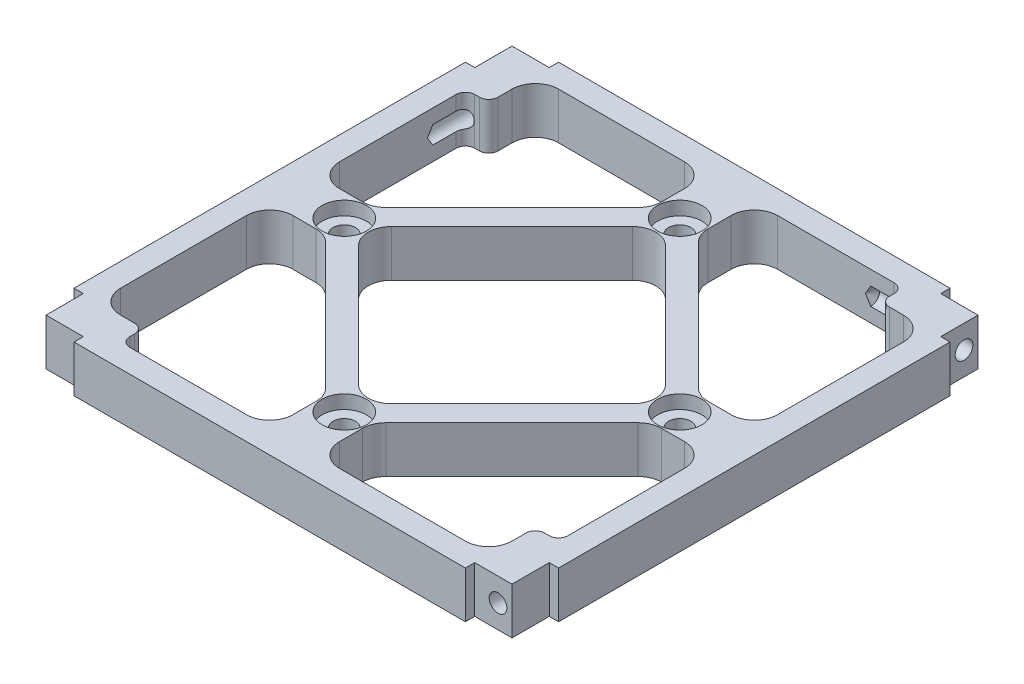
SolidWorks part; units mm, degrees
material "6061-T6 (SS)"
ref_plane "Front Plane" through (0, 0, 0) normal (0, 0, 1) x (1, 0, 0)
ref_plane "Top Plane" through (0, 0, 0) normal (0, 1, 0) x (1, 0, 0)
ref_plane "Right Plane" through (0, 0, 0) normal (1, 0, 0) x (0, 0, -1)
sketch "Sketch1" plane through (0, 0, 0) normal (0, 1, 0) x (1, 0, 0)
  line L0 (-42, 47) -> (-42, 37)
  line L1 (-52, 52) -> (52, 52)
  line L2 (-52, 52) -> (-52, -52)
  line L3 (-52, -52) -> (52, -52)
  line L4 (52, 52) -> (52, -52)
  line L5 (-47, 5) -> (-35, 5)
  line L6 (-35, 5) -> (-5, 35)
  line L7 (-5, 35) -> (-5, 47)
  line L8 (-5, 47) -> (-42, 47)
  line L9 (0, 0) -> (0, 76.3292) construction
  line L10 (0, 0) -> (-78.8537, 0) construction
  line L11 (0, 0) -> (-66.7994, 66.7994) construction
  line L12 (-32.9289, 0) -> (0, 32.9289)
  line L13 (0, 32.9289) -> (32.9289, 0)
  line L14 (32.9289, 0) -> (0, -32.9289)
  line L15 (0, -32.9289) -> (-32.9289, 0)
  line L16 (5, 47) -> (5, 35)
  line L17 (37, 47) -> (5, 47)
  line L18 (37, 42) -> (37, 47)
  line L19 (47, 42) -> (37, 42)
  line L20 (47, 5) -> (47, 42)
  line L21 (35, 5) -> (47, 5)
  line L22 (5, 35) -> (35, 5)
  line L23 (47, -5) -> (35, -5)
  line L24 (47, -37) -> (47, -5)
  line L25 (42, -37) -> (47, -37)
  line L26 (42, -47) -> (42, -37)
  line L27 (5, -47) -> (42, -47)
  line L28 (5, -35) -> (5, -47)
  line L29 (35, -5) -> (5, -35)
  line L30 (-5, -47) -> (-5, -35)
  line L31 (-42, 37) -> (-47, 37)
  line L32 (-47, 37) -> (-47, 5)
  line L33 (-37, -47) -> (-5, -47)
  line L34 (-37, -42) -> (-37, -47)
  line L35 (-47, -42) -> (-37, -42)
  line L36 (-47, -5) -> (-47, -42)
  line L37 (-35, -5) -> (-47, -5)
  line L38 (-5, -35) -> (-35, -5)
  point P36 (0.1996, 0.1996)
  point P45 (0, 0)
  dimension "D1" = 104
  dimension "D2" = 5
  dimension "D3" = 5
  dimension "D4" = 5
  dimension "D5" = 5
  dimension "D6" = 5
  dimension "D7" = 12
  dimension "D8" = 10
  dimension "D9" = 10
  dimension "D10" = 4
extrude "Boss-Extrude1" add sketch "Sketch1" along normal blind 10
fillet "Fillet1" radius 5 24 edges at (32.9289, 5, 0) (0, 5, 32.9289) (-32.9289, 5, 0) (0, 5, -32.9289) (-5, 5, -47) (-5, 5, -35) (-35, 5, -5) (-47, 5, 42) (-47, 5, 5) (-35, 5, 5) (-5, 5, 35) (-5, 5, 47) (42, 5, 47) (47, 5, 5) (35, 5, 5) (5, 5, 35) (5, 5, 47) (47, 5, -42) (47, 5, -5) (35, 5, -5) (5, 5, -35) (5, 5, -47) (-42, 5, -47) (-47, 5, -5)
sketch "Sketch2" plane through (0, 10, 0) normal (0, 1, 0) x (1, 0, 0)
  line L0 (-52, 52) -> (-42, 52)
  line L1 (52, 52) -> (-52, 52) construction
  line L2 (-42, 52) -> (-42, 50)
  line L3 (-42, 50) -> (-50, 50)
  line L4 (-50, 50) -> (-50, 42)
  line L5 (-50, 42) -> (-52, 42)
  line L6 (-52, 52) -> (-52, -52) construction
  line L7 (-52, 42) -> (-52, 52)
  dimension "D1" = 2
  dimension "D2" = 10
extrude "Cut-Extrude1" cut sketch "Sketch2" against normal through all
ref_axis "Axis1" through (0, 10.5, 0) along (0, -1, 0)
pattern_circular "CirPattern1" count 4 over 360 about axis through (0, 10.5, 0) along (0, -1, 0) of "Cut-Extrude1"
hole_wizard "CBORE for #12 Binding Head Machine Screw1" positions "Sketch3" profile "Sketch5" counterbore size "#12" standard "ANSI Inch" end condition through all
sketch "Sketch3" plane through (0, 10, 0) normal (0, 1, 0) x (1, 0, 0)
  line L2 (0, 36) -> (36, 0)
  line L3 (-36, 0) -> (0, -36)
  line L4 (36, 0) -> (0, -36)
  line L6 (0, 0) -> (0, 48.9753) construction
  line L7 (0, 0) -> (-18.2924, 0) construction
  line L9 (-36, 0) -> (0, 36)
  line L11 (-3.5355, 29.3934) -> (-29.3934, 3.5355) construction
  point P0 (0, 36)
  point P199 (-36, 0)
  point P315 (0, -36)
  point P316 (36, 0)
  dimension "D1" = 36
sketch "Sketch5" plane through (0, 10, -36) normal (1, 0, 0) x (0, 0, 1)
  line L0 (0, 0) -> (0, 10)
  line L1 (0, 10) -> (2.4003, 10)
  line L3 (2.4003, 10) -> (2.4003, 2.921)
  line L4 (2.4003, 2.921) -> (4.7625, 2.921)
  line L5 (4.7625, 2.921) -> (4.7625, 0)
  line L7 (4.7625, 0) -> (0, 0)
  line L11 (0, -6.35) -> (0, 107.95) construction
  dimension "Thru Hole Dia." = 4.8006
  dimension "Thru Hole Depth" = 10
  dimension "C'Bore Dia." = 9.525
  dimension "C'Bore Depth" = 2.921
fillet "Fillet3" radius 2 8 edges at (-37, 5, 42) (-37, 5, 47) (42, 5, 37) (47, 5, 37) (37, 5, -42) (37, 5, -47) (-47, 5, -37) (-42, 5, -37)
hole_wizard "#10-24 Tapped Hole1" positions "Sketch6" profile "Sketch9" tap size "#10-24" standard "ANSI Inch"
sketch "Sketch6" plane through (50, 0, 0) normal (1, 0, 0) x (0, 0, -1)
  line L2 (42, 10) -> (52, 0)
  point P0 (47, 5)
  point P13 (47, 5)
sketch "Sketch9" plane through (50, 5, -47) normal (0, 1, 0) x (0, 0, -1)
  line L0 (0, 0) -> (0, 21.1408)
  line L1 (0, 21.1408) -> (1.8986, 20)
  line L2 (1.8986, 20) -> (1.8986, 0)
  line L5 (1.8986, 0) -> (0, 0)
  line L10 (0, 21.1408) -> (-1.8987, 20) construction
  line L11 (0, -6.35) -> (0, 107.95) construction
  dimension "Tap Drill Dia." = 3.7973
  dimension "Tap Drill Depth" = 20
  dimension "Drill Angle" = 118
cosmetic thread "Hole Thread1" parameters "D1"=9.65, "D2"=4.826
pattern_circular "CirPattern5" count 4 over 360 about axis through (0, 10.5, 0) along (0, -1, 0) of "#10-24 Tapped Hole1"
